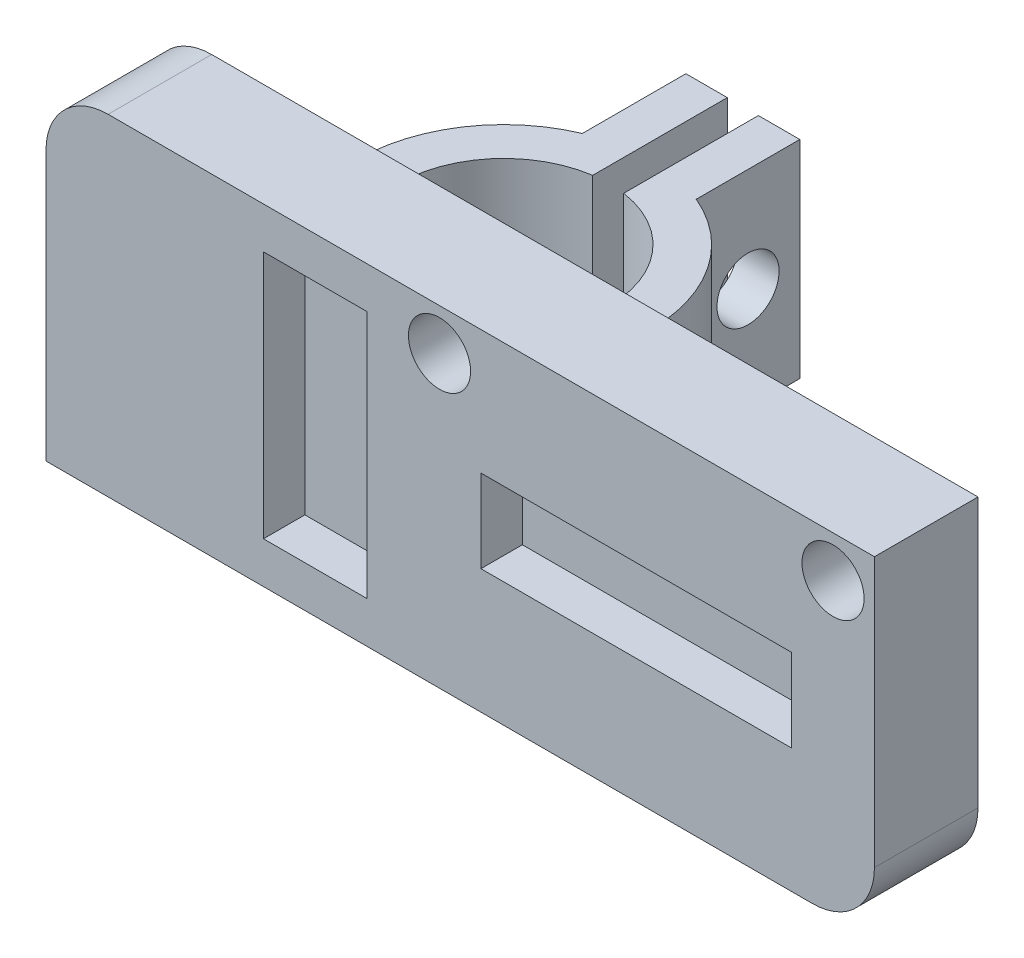
SolidWorks part; units mm, degrees
ref_plane "Plano frontal" through (0, 0, 0) normal (0, 0, 1) x (1, 0, 0)
ref_plane "Plano superior" through (0, 0, 0) normal (0, 1, 0) x (1, 0, 0)
ref_plane "Plano direito" through (0, 0, 0) normal (1, 0, 0) x (0, 0, -1)
sketch "Esboço1" plane through (0, 0, 0) normal (0, 0, 1) x (1, 0, 0)
  line L7 (3, 16) -> (40, 16)
  line L8 (40, 16) -> (40, 3)
  line L9 (0, 0) -> (37, 0)
  line L12 (0, 13) -> (0, 0)
  line L17 (15.5, 14) -> (10.5, 14)
  line L18 (15.5, 2) -> (15.5, 14)
  line L19 (10.5, 2) -> (15.5, 2)
  line L20 (10.5, 14) -> (10.5, 2)
  line L25 (36, 10) -> (21, 10)
  line L26 (36, 6) -> (36, 10)
  line L27 (36, 6) -> (21, 6)
  line L28 (21, 10) -> (21, 6)
  arc A0 (0, 13) -> (3, 16) centre (3, 13) cw
  arc A1 (40, 3) -> (37, 0) centre (37, 3) cw
  circle A2 centre (19, 14) radius 1.5
  circle A4 centre (38, 14) radius 1.5
  dimension "D2" = 3
  dimension "D3" = 3
  dimension "D5" = 3
  dimension "D6" = 3
  dimension "D1" = 16
  dimension "D4" = 40
  dimension "D7" = 2
  dimension "D8" = 21
  dimension "D9" = 2
  dimension "D10" = 2
  dimension "D11" = 15
  dimension "D12" = 4
  dimension "D13" = 12
  dimension "D14" = 5
  dimension "D15" = 2
  dimension "D16" = 10.5
  dimension "D17" = 5.5
  dimension "D18" = 6
extrude "Ressalto-extrusão1" add sketch "Esboço1" against normal blind 5 contours A1 L8 L7 A0 L12 L9 A4 A2 L28 L25 L26 L27 L20 L17 L18 L19 | L17 L20 L19 L18 | L25 L28 L27 L26 region at (19.5813, 7.831, 0) region at (13, 8, 0) region at (28.5, 8, 0)
extrude "Corte-extrusão1" cut sketch "Esboço1<3>" against normal blind 2 contours L17 L20 L19 L18 | L25 L28 L27 L26 region at (13, 8, 0) region at (28.5, 8, 0)
sketch "Esboço1<3>" plane through (0, 0, 0) normal (0, 0, 1) x (1, 0, 0) same geometry as "Esboço1"
sketch "Esboço2" plane through (0, 0, 0) normal (0, -1, 0) x (1, 0, 0)
  line L0 (4.9, -5) -> (19.1, -5)
  line L1 (0, -5) -> (37, -5) construction
  line L2 (19.1, -5) -> (19.1, -10.1)
  line L3 (4.9, -10.1) -> (4.9, -5)
  line L4 (12, -10.0005) -> (12, -20.6671) construction
  line L5 (12.75, -15.1446) -> (12.75, -21.6458)
  line L6 (11.25, -15.1446) -> (11.25, -21.6458)
  line L7 (12.75, -21.6458) -> (14.75, -21.6458)
  line L8 (14.75, -21.6458) -> (14.75, -16.6458)
  line L9 (11.25, -21.6458) -> (9.25, -21.6458)
  line L10 (9.25, -21.6458) -> (9.25, -16.6458)
  line L11 (0, -5) -> (0, 0) construction
  arc A0 (19.1, -10.1) -> (14.75, -16.6458) centre (12, -10.1) cw
  arc A1 (12.75, -15.1446) -> (11.25, -15.1446) centre (12, -10.1) ccw
  arc A3 (9.25, -16.6458) -> (4.9, -10.1) centre (12, -10.1) cw
  line M12 (0, -5) -> (37, -5)
  dimension "D2" = 10.2
  dimension "D3" = 2
  dimension "D1" = 2
  dimension "D6" = 12
  dimension "D4" = 1.5
  dimension "D5" = 5
extrude "Ressalto-extrusão2" add sketch "Esboço2" against normal blind 10 contours A1 L5 L7 L8 A0 L2 L0 | A3 L10 L9 L6 A1 L3 M12 region at (15.55, 0, -5.181) region at (8.45, 0, -5.181)
sketch "Esboço3" plane through (14.75, 0, 0) normal (1, 0, 0) x (0, 0, -1)
  line L0 (19.1458, 10) -> (19.1458, 0) construction
  line L1 (21.6458, 10) -> (16.6458, 10) construction
  line L2 (21.6458, 0) -> (16.6458, 0) construction
  circle A0 centre (19.1458, 5) radius 1.5
  dimension "D1" = 3
extrude "Corte-extrusão2" cut sketch "Esboço3" against normal blind 10
